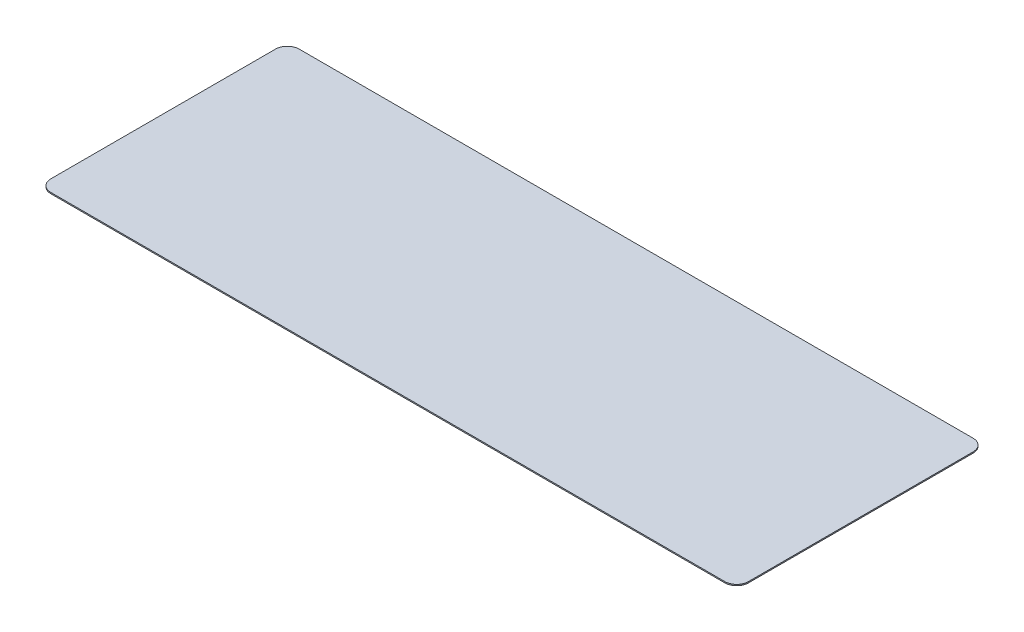
SolidWorks part; units mm, degrees
material "AISI 1020 Steel, Cold Rolled"
ref_plane "Front Plane" through (0, 0, 0) normal (0, 0, 1) x (1, 0, 0)
ref_plane "Top Plane" through (0, 0, 0) normal (0, 1, 0) x (1, 0, 0)
ref_plane "Right Plane" through (0, 0, 0) normal (1, 0, 0) x (0, 0, -1)
sketch "Sketch1" plane through (0, 0, 0) normal (0, 1, 0) x (1, 0, 0)
  line L1 (-295, 105) -> (295, 105)
  line L2 (-295, 105) -> (-295, -105)
  line L3 (-295, -105) -> (295, -105)
  line L4 (295, 105) -> (295, -105)
  line L5 (-295, 105) -> (295, -105) construction
  line L6 (-295, -105) -> (295, 105) construction
  point P0 (0, 0)
  dimension "D1" = 590
  dimension "D2" = 210
extrude "Boss-Extrude1" add sketch "Sketch1" along normal blind 1
fillet "Fillet1" radius 10 4 edges at (-295, 0.5, 105) (295, 0.5, 105) (295, 0.5, -105) (-295, 0.5, -105)
